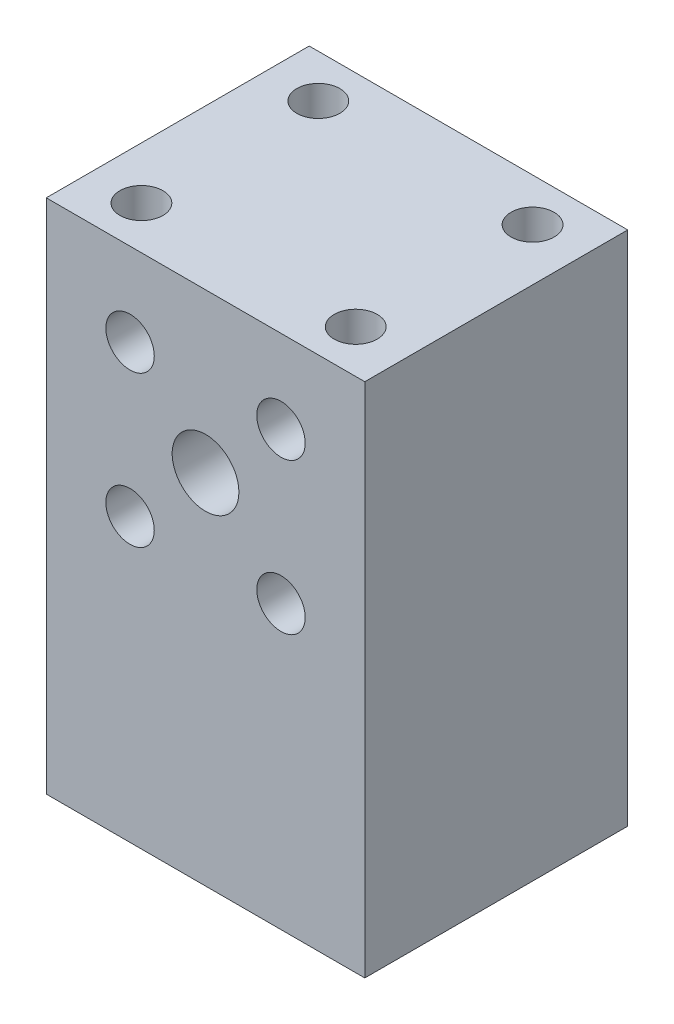
SolidWorks part; units mm, degrees
ref_plane "Front Plane" through (0, 0, 0) normal (0, 0, 1) x (1, 0, 0)
ref_plane "Top Plane" through (0, 0, 0) normal (0, 1, 0) x (1, 0, 0)
ref_plane "Right Plane" through (0, 0, 0) normal (1, 0, 0) x (0, 0, -1)
sketch "Sketch1" plane through (0, 0, 0) normal (0, 1, 0) x (1, 0, 0)
  line L0 (47, 0) -> (47, 38.8)
  line L1 (4.5, 34.4) -> (0, 34.4) construction
  line L2 (42.5, 34.4) -> (47, 34.4) construction
  line B0 (0, 38.8) -> (254, 38.8)
  line B1 (0, 38.8) -> (0, 0)
  line B2 (0, 0) -> (254, 0)
  line B3 (254, 38.8) -> (254, 0)
  circle B4 centre (249.5, 34.4) radius 2.5
  circle B5 centre (249.5, 4.4) radius 2.5
  circle B6 centre (211.5, 4.4) radius 2.5
  circle B7 centre (211.5, 34.4) radius 2.627
  circle B8 centre (42.5, 34.4) radius 2.5
  circle B9 centre (42.5, 4.4) radius 2.5
  circle B10 centre (4.5, 4.4) radius 2.5
  circle B11 centre (4.5, 34.4) radius 2.627
sketch_block_instance "Block-LateralDirSliderMounting-1"
sketch_block "Block-LateralDirSliderMounting"
sketch "Sketch2" plane through (0, 0, 0) normal (0, 0, 1) x (1, 0, 0)
  line L0 (0, 73.2465) -> (47, 73.2465)
  line L1 (0, 0) -> (47, 0)
  line L2 (0, 0) -> (0, 107)
  line L3 (0, 107) -> (47, 107)
  line L4 (47, 0) -> (47, 107)
  point P5 (12.3645, 38.1)
  point P10 (23.5, 0)
  circle B0 centre (23.5, 52.8074) radius 20.4391
  circle B1 centre (34.6355, 63.9429) radius 3.5719
  circle B2 centre (34.6355, 41.6719) radius 3.5719
  circle B3 centre (12.3645, 41.6719) radius 3.5719
  circle B4 centre (12.3645, 63.9429) radius 3.5719
  circle B5 centre (23.5, 52.8074) radius 4.9213
  dimension "D1" = 107
  dimension "D2" = 38.1
sketch_block_instance "Block-RailTravellerMounting-1"
sketch_block "Block-RailTravellerMounting"
extrude "Boss-Extrude1" add sketch "Sketch1" along normal blind 76.2 contours B1 B2 L0 B0 B11 B10 B9 B8 | B9 | B10 | B11 | B8 region at (23.5223, 0, -19.3824) region at (42.5, 0, -34.4) region at (42.5, 0, -4.4) region at (4.5, 0, -4.4) region at (4.5, 0, -34.4)
extrude "Cut-Extrude1" cut sketch "Sketch2" against normal through all contours B4 | B1 | B2 | B5 | B3 region at (34.6355, 63.9429, 0) region at (34.6355, 41.6719, 0) region at (12.3645, 41.6719, 0) region at (12.3645, 63.9429, 0) region at (23.5, 52.8074, 0)
extrude "Cut-Extrude2" cut sketch "Sketch1<8>" along normal blind 38.1 contours B11 | B10 | B9 | B8 region at (42.5, 0, -34.4) region at (42.5, 0, -4.4) region at (4.5, 0, -4.4) region at (4.5, 0, -34.4)
sketch "Sketch1<8>" plane through (0, 0, 0) normal (0, 1, 0) x (1, 0, 0) same geometry as "Sketch1"
sketch "Sketch4" plane through (0, 0, -38.8) normal (0, 0, -1) x (-1, 0, 0)
  circle A0 centre (-23.5, 52.8074) radius 9.525
  dimension "D1" = 19.05
extrude "Cut-Extrude4" cut sketch "Sketch4" against normal blind 21.0185
sketch "Sketch5" plane through (0, 76.2, 0) normal (0, 1, 0) x (1, 0, 0)
  line L1 (47, 0) -> (0, 0) construction
  line L2 (47, 0) -> (47, 38.8) construction
  line L3 (47, 38.8) -> (0, 38.8) construction
  line L4 (0, 0) -> (0, 38.8) construction
  line L5 (47, 0) -> (0, 38.8) construction
  line L6 (47, 38.8) -> (0, 0) construction
  line L7 (7.692, 32.45) -> (39.308, 32.45) construction
  line L8 (7.692, 32.45) -> (7.692, 6.35) construction
  line L9 (7.692, 6.35) -> (39.308, 6.35) construction
  line L10 (39.308, 32.45) -> (39.308, 6.35) construction
  circle A0 centre (7.692, 32.45) radius 3.175
  circle A1 centre (39.308, 32.45) radius 3.175
  circle A2 centre (39.308, 6.35) radius 3.175
  circle A3 centre (7.692, 6.35) radius 3.175
  point P0 (23.5, 19.4)
  dimension "D2" = 6.35
  dimension "D1" = 6.35
extrude "Cut-Extrude5" cut sketch "Sketch5" against normal blind 6.35
